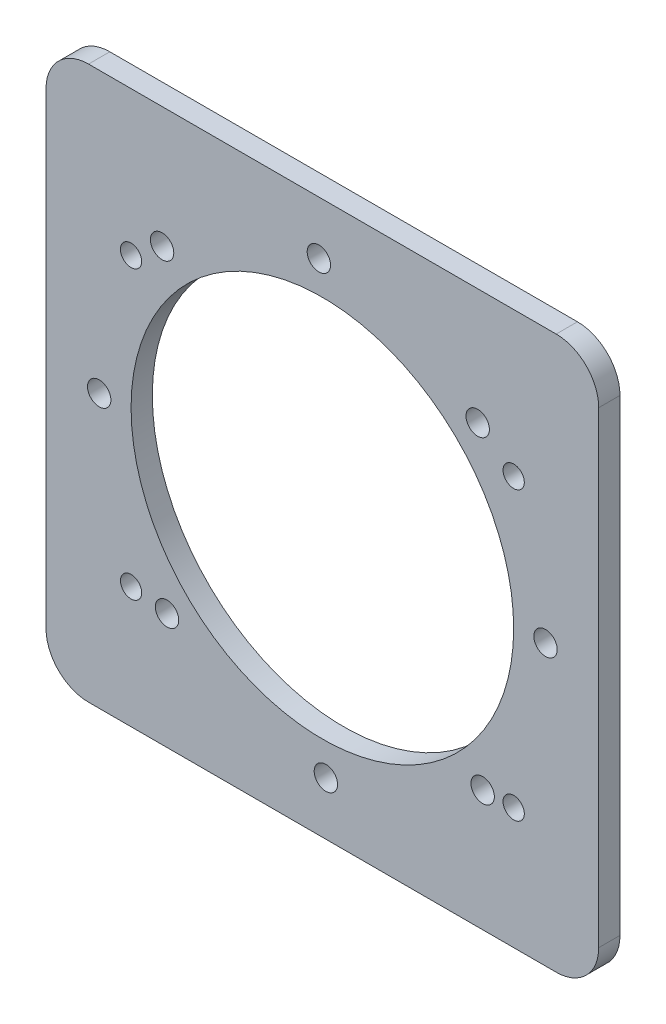
SolidWorks part; units mm, degrees
material "默认 (3)"
ref_plane "前视基准面" through (0, 0, 0) normal (0, 0, 1) x (1, 0, 0)
ref_plane "上视基准面" through (0, 0, 0) normal (0, 1, 0) x (1, 0, 0)
ref_plane "右视基准面" through (0, 0, 0) normal (1, 0, 0) x (0, 0, -1)
other "Configuration Table"
sketch "草图1" plane through (0, 0, 0) normal (0, 0, 1) x (1, 0, 0)
  line L1 (-65, 65) -> (65, 65)
  line L2 (-65, 65) -> (-65, -65)
  line L3 (-65, -65) -> (65, -65)
  line L4 (65, 65) -> (65, -65)
  line L5 (-65, 65) -> (65, -65) construction
  line L6 (-65, -65) -> (65, 65) construction
  point P0 (0, 0)
  dimension "D1" = 130
  dimension "D2" = 130
extrude "凸台-拉伸1" add sketch "草图1" along normal blind 5
sketch "草图5" plane through (0, 0, 0) normal (0, 0, -1) x (-1, 0, 0)
  circle A0 centre (0, 0) radius 45
  dimension "D1" = 90
extrude "切除-拉伸2" cut sketch "草图5" against normal up to next
fillet "圆角1" radius 10 4 edges at (65, 65, 2.5) (65, -65, 2.5) (-65, -65, 2.5) (-65, 65, 2.5)
sketch "草图6" plane through (0, 0, 0) normal (0, 0, -1) x (-1, 0, 0)
  arc A6 (39.6758, 38.4499) -> (35.7262, 34.6223) centre (37.701, 36.5361) ccw
  arc A7 (35.7262, 34.6223) -> (39.6758, 38.4499) centre (37.701, 36.5361) ccw
  arc A8 (39.6758, 38.4499) -> (35.7262, 34.6223) centre (37.701, 36.5361) ccw
  arc A9 (35.7262, 34.6223) -> (39.6758, 38.4499) centre (37.701, 36.5361) ccw
  arc A10 (54.4684, 1.0901) -> (50.5187, -2.7375) centre (52.4935, -0.8237) ccw
  arc A11 (50.5187, -2.7375) -> (54.4684, 1.0901) centre (52.4935, -0.8237) ccw
  arc A12 (54.4684, 1.0901) -> (50.5187, -2.7375) centre (52.4935, -0.8237) ccw
  arc A13 (50.5187, -2.7375) -> (54.4684, 1.0901) centre (52.4935, -0.8237) ccw
  arc A14 (38.5109, -35.7872) -> (34.5613, -39.6148) centre (36.5361, -37.701) ccw
  arc A15 (34.5613, -39.6148) -> (38.5109, -35.7872) centre (36.5361, -37.701) ccw
  arc A16 (38.5109, -35.7872) -> (34.5613, -39.6148) centre (36.5361, -37.701) ccw
  arc A17 (34.5613, -39.6148) -> (38.5109, -35.7872) centre (36.5361, -37.701) ccw
  arc A18 (1.1511, -50.5797) -> (-2.7985, -54.4073) centre (-0.8237, -52.4935) ccw
  arc A19 (-2.7985, -54.4073) -> (1.1511, -50.5797) centre (-0.8237, -52.4935) ccw
  arc A20 (1.1511, -50.5797) -> (-2.7985, -54.4073) centre (-0.8237, -52.4935) ccw
  arc A21 (-2.7985, -54.4073) -> (1.1511, -50.5797) centre (-0.8237, -52.4935) ccw
  arc A22 (-35.7262, -34.6223) -> (-39.6758, -38.4499) centre (-37.701, -36.5361) ccw
  arc A23 (-39.6758, -38.4499) -> (-35.7262, -34.6223) centre (-37.701, -36.5361) ccw
  arc A24 (-35.7262, -34.6223) -> (-39.6758, -38.4499) centre (-37.701, -36.5361) ccw
  arc A25 (-39.6758, -38.4499) -> (-35.7262, -34.6223) centre (-37.701, -36.5361) ccw
  arc A26 (-50.5187, 2.7375) -> (-54.4684, -1.0901) centre (-52.4935, 0.8237) ccw
  arc A27 (-54.4684, -1.0901) -> (-50.5187, 2.7375) centre (-52.4935, 0.8237) ccw
  arc A28 (-50.5187, 2.7375) -> (-54.4684, -1.0901) centre (-52.4935, 0.8237) ccw
  arc A29 (-54.4684, -1.0901) -> (-50.5187, 2.7375) centre (-52.4935, 0.8237) ccw
  arc A30 (-34.5613, 39.6148) -> (-38.5109, 35.7872) centre (-36.5361, 37.701) ccw
  arc A31 (-38.5109, 35.7872) -> (-34.5613, 39.6148) centre (-36.5361, 37.701) ccw
  arc A32 (-34.5613, 39.6148) -> (-38.5109, 35.7872) centre (-36.5361, 37.701) ccw
  arc A33 (-38.5109, 35.7872) -> (-34.5613, 39.6148) centre (-36.5361, 37.701) ccw
  arc A34 (2.7985, 54.4073) -> (-1.1511, 50.5797) centre (0.8237, 52.4935) ccw
  arc A35 (-1.1511, 50.5797) -> (2.7985, 54.4073) centre (0.8237, 52.4935) ccw
  arc A36 (2.7985, 54.4073) -> (-1.1511, 50.5797) centre (0.8237, 52.4935) ccw
  arc A37 (-1.1511, 50.5797) -> (2.7985, 54.4073) centre (0.8237, 52.4935) ccw
  dimension "D2" = 0
  dimension "D3" = 0
  dimension "D4" = 0
  dimension "D5" = 0
  dimension "D6" = 0
  dimension "D7" = 0
  dimension "D8" = 0
  dimension "D9" = 0
extrude "切除-拉伸3" cut sketch "草图6" against normal blind 10
sketch "草图7" plane through (0, 0, 5) normal (0, 0, 1) x (1, 0, 0)
  circle A0 centre (45, 31.0343) radius 2.5 construction
  circle A1 centre (45, -36.4657) radius 2.5 construction
  circle A2 centre (-45, -36.4657) radius 2.5 construction
  circle A3 centre (-45, 31.0343) radius 2.5 construction
  circle A4 centre (45, 31.0343) radius 2.5
  circle A5 centre (45, -36.4657) radius 2.5
  circle A6 centre (-45, -36.4657) radius 2.5
  circle A7 centre (-45, 31.0343) radius 2.5
extrude "切除-拉伸4" cut sketch "草图7" against normal through all
